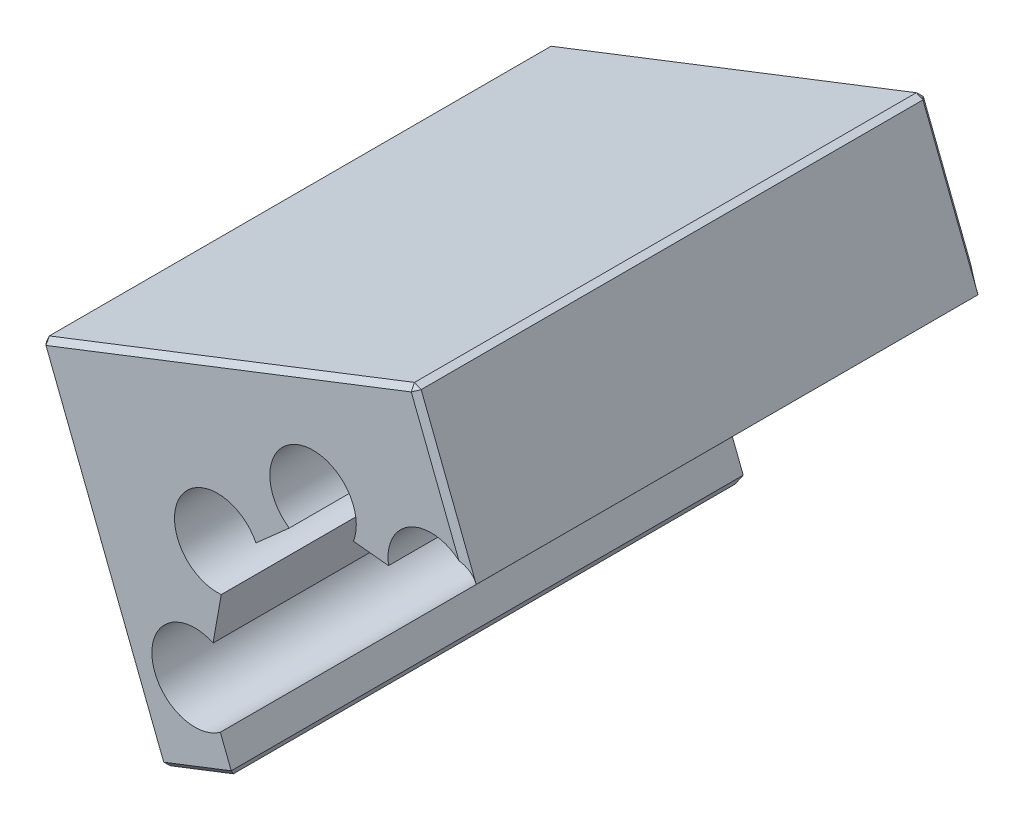
SolidWorks part; units mm, degrees
ref_plane "前基準面" through (0, 0, 0) normal (0, 0, 1) x (1, 0, 0)
ref_plane "上基準面" through (0, 0, 0) normal (0, 1, 0) x (1, 0, 0)
ref_plane "右基準面" through (0, 0, 0) normal (1, 0, 0) x (0, 0, -1)
sketch "草圖1" plane through (0, 0, 12.6059) normal (0, 0, 1) x (1, 0, 0)
  line L0 (-121.0055, -94.6668) -> (-109.956, -32.2463) construction
  line L1 (-109.956, -32.2463) -> (-63.2989, 9.2018) construction
  line L2 (-63.2989, 9.2018) -> (-5.7089, 3.2255) construction
  line L3 (-121.0055, -94.6668) -> (-112.1178, -75.6402) construction
  line L4 (-112.1178, -75.6402) -> (-108.1397, -53.1676)
  line L5 (-108.1397, -53.1676) -> (-109.956, -32.2463) construction
  line L6 (-109.956, -32.2463) -> (-91.1815, -22.8379) construction
  line L7 (-91.1815, -22.8379) -> (-74.9152, -8.4262)
  line L8 (-74.9152, -8.4262) -> (-63.2989, 9.2018) construction
  line L9 (-63.2989, 9.2018) -> (-43.5799, 1.6622) construction
  line L10 (-43.5799, 1.6622) -> (-26.446, -0.0869)
  line L11 (-26.446, -0.0869) -> (-5.7089, 3.2255) construction
  line L12 (-108.5754, -111.5928) -> (-102.3514, -127.5624)
  line L13 (-92.2541, -117.2308) -> (16.6857, -396.7521) construction
  line L14 (13.8576, 10.8513) -> (-13.9295, 82.1483)
  line L15 (-102.3514, -127.5624) -> (-137.6384, -141.3151)
  line L16 (-137.6384, -141.3151) -> (-196.9331, 10.825)
  line L17 (-196.9331, 10.825) -> (-13.9295, 82.1483)
  arc A1 (-112.1178, -75.6402) -> (-108.5754, -111.5928) centre (-121.0055, -94.6668) ccw
  arc A2 (-91.1815, -22.8379) -> (-108.1397, -53.1676) centre (-109.956, -32.2463) ccw
  arc A3 (-43.5799, 1.6622) -> (-74.9152, -8.4262) centre (-63.2989, 9.2018) ccw
  arc A4 (13.8576, 10.8513) -> (-26.446, -0.0869) centre (-5.7089, 3.2255) ccw
  dimension "D1" = 15
  dimension "D2" = 15
  dimension "D3" = 15
  dimension "D4" = 15
  dimension "D5" = 15
  dimension "D6" = 15
extrude "填料-伸長2" add sketch "草圖1" against normal blind 250
chamfer "導角1" distance 2.5 angle 45 12 edges at (-105.4313, 46.4867, -237.3941) (-0.036, 46.4998, -237.3941) (-13.9295, 82.1483, -112.3941) (-167.2857, -65.245, -237.3941) (-196.9331, 10.825, -112.3941) (-102.3514, -127.5624, -112.3941) (-119.9949, -134.4387, -237.3941) (-137.6384, -141.3151, -112.3941) (-119.9949, -134.4387, 12.6059) (-167.2857, -65.245, 12.6059) (-105.4313, 46.4867, 12.6059) (-0.036, 46.4998, 12.6059)
equation "\"ㄉ200\"=10"
